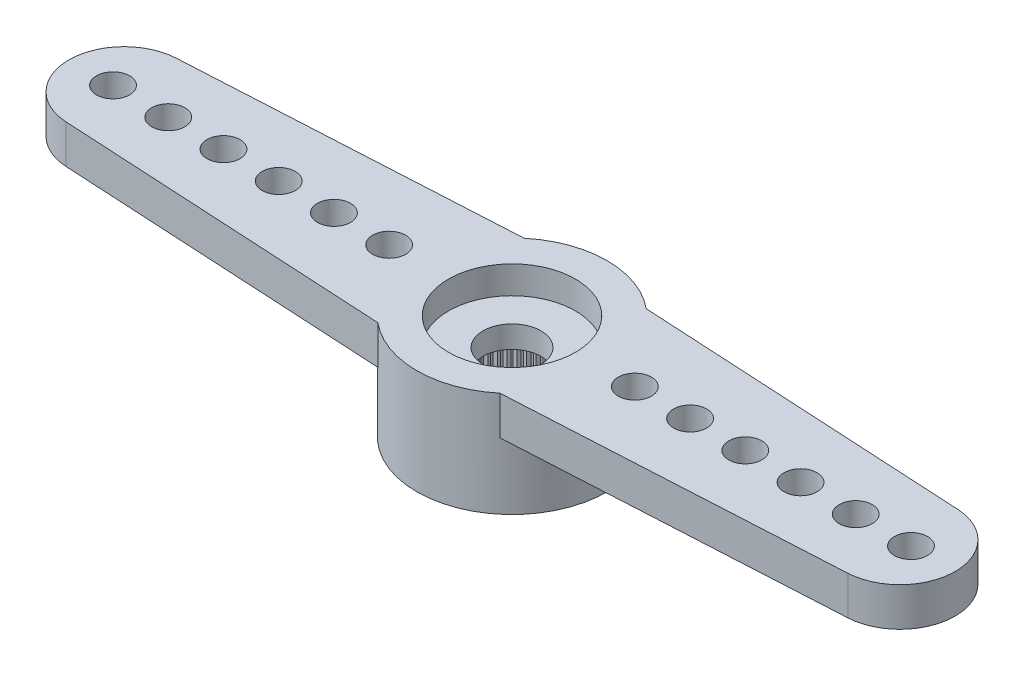
SolidWorks part; units mm, degrees
material "PVC Rígido"
ref_plane "Plano frontal" through (0, 0, 0) normal (0, 0, 1) x (1, 0, 0)
ref_plane "Plano superior" through (0, 0, 0) normal (0, 1, 0) x (1, 0, 0)
ref_plane "Plano direito" through (0, 0, 0) normal (1, 0, 0) x (0, 0, -1)
sketch "Esboço1" plane through (0, 0, 0) normal (0, 1, 0) x (1, 0, 0)
  line L0 (0, 0) -> (-14.05, 0) construction
  line L1 (-14.1591, 1.997) -> (-2.2091, 2.65)
  line L2 (-2.2091, -2.65) -> (-14.1591, -1.997)
  arc A0 (-2.2091, -2.65) -> (-2.2091, 2.65) centre (0, 0) ccw
  arc A1 (-14.1591, 1.997) -> (-14.1591, -1.997) centre (-14.05, 0) ccw
  dimension "D1" = 6.9
  dimension "D2" = 4
  dimension "D3" = 19.5
  dimension "D4" = 5.3
extrude "Ressalto-extrusão1" add sketch "Esboço1" against normal blind 1.4
sketch "Esboço2" plane through (0, -1.4, 0) normal (0, -1, 0) x (1, 0, 0)
  arc A0 (-2.2091, -2.65) -> (-2.2091, 2.65) centre (0, 0) ccw construction
  circle A1 centre (0, 0) radius 3.45
extrude "Ressalto-extrusão2" add sketch "Esboço2" along normal offset from surface (2.4 mm away) 3.8 up to face at (-7.242, 0, 0)
hole_wizard "Furo4" positions "Esboço9" profile "Esboço10" legacy end condition through all
sketch "Esboço9" plane through (0, 0, 0) normal (0, 1, 0) x (1, 0, 0)
  line L1 (-14.45, 0) -> (0, 0) construction
  arc A2 (-14.1591, 1.997) -> (-14.1591, -1.997) centre (-14.05, 0) ccw construction
  point P0 (-14.45, 0)
  point P19 (-16.05, 0)
  dimension "D1" = 1.6
sketch "Esboço10" plane through (-14.45, 0, 0) normal (1, 0, 0) x (0, 0, 1)
  line L0 (0, 0) -> (0, 3.8)
  line L1 (0, 3.8) -> (0.6, 3.8)
  line L2 (0.6, 3.8) -> (0.6, 0)
  line L3 (0.6, 0) -> (0, 0)
  line L4 (0, 110) -> (0, -10) construction
  dimension "Diameter" = 1.2
  dimension "Depth" = 3.8
pattern_linear "Padrão linear1" count 6 spacing 2 along (1, 0, 0) of "Furo4"
pattern_circular "PadrãoCircular2" count 2 over 360 about axis through (0, -1.4, 0) along (0, 1, 0) of "Ressalto-extrusão1", "Furo4", "Padrão linear1"
hole_wizard "Furo1" positions "Esboço3" profile "Esboço4" legacy
sketch "Esboço3" plane through (0, -3.8, 0) normal (0, -1, 0) x (-1, 0, 0)
  point P0 (0, 0)
sketch "Esboço4" plane through (0, -3.8, 0) normal (1, 0, 0) x (0, 0, -1)
  line L0 (0, 0) -> (0, 2)
  line L1 (0, 2) -> (2.475, 2)
  line L2 (2.475, 2) -> (2.475, 0)
  line L3 (2.475, 0) -> (0, 0)
  line L4 (0, 110) -> (0, -10) construction
  dimension "Diameter" = 4.95
  dimension "Depth" = 2
hole_wizard "Furo2" positions "Esboço5" profile "Esboço6" legacy
sketch "Esboço5" plane through (0, 0, 0) normal (0, 1, 0) x (1, 0, 0)
  point P0 (0, 0)
sketch "Esboço6" plane through (0, 0, 0) normal (1, 0, 0) x (0, 0, 1)
  line L0 (0, 0) -> (0, 1)
  line L1 (0, 1) -> (2.3, 1)
  line L2 (2.3, 1) -> (2.3, 0)
  line L3 (2.3, 0) -> (0, 0)
  line L4 (0, 110) -> (0, -10) construction
  dimension "Diameter" = 4.6
  dimension "Depth" = 1
hole_wizard "Furo3" positions "Esboço7" profile "Esboço8" legacy end condition through all
sketch "Esboço7" plane through (0, 0, 0) normal (0, 1, 0) x (1, 0, 0)
  point P0 (0, 0)
sketch "Esboço8" plane through (0, 0, 0) normal (1, 0, 0) x (0, 0, 1)
  line L0 (0, 0) -> (0, 3.8)
  line L1 (0, 3.8) -> (1.05, 3.8)
  line L2 (1.05, 3.8) -> (1.05, 0)
  line L3 (1.05, 0) -> (0, 0)
  line L4 (0, 110) -> (0, -10) construction
  dimension "Diameter" = 2.1
  dimension "Depth" = 3.8
sketch "Esboço11" plane through (0, -3.8, 0) normal (0, -1, 0) x (1, 0, 0)
  line L0 (-0.0981, 2.4731) -> (0, 2.375)
  line L1 (0, 2.375) -> (0.0981, 2.4731)
  line L2 (0, 0) -> (0, 2.475) construction
  circle A0 centre (0, 0) radius 2.375 construction
  circle A1 centre (0, 0) radius 2.475
  arc A2 (0.0981, 2.4731) -> (-0.0981, 2.4731) centre (0, 0) ccw
  dimension "D3" = 4.75
  dimension "D2" = 0.1
  dimension "D1" = 0
extrude "Ressalto-extrusão3" add sketch "Esboço11" against normal up to surface (2 mm away) up to face at (0, -1.8, 1.05)
pattern_circular "PadrãoCircular1" count 60 over 360 about axis through (0, -1.4, 0) along (0, 1, 0) of "Ressalto-extrusão3"
